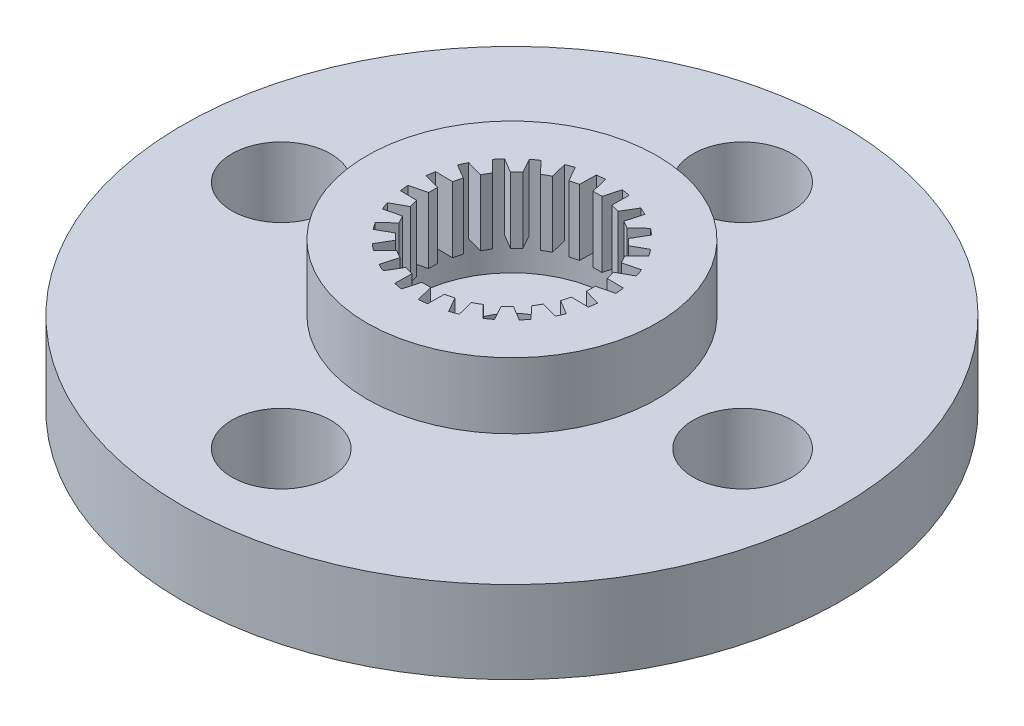
SolidWorks part; units mm, degrees
other "标注1"
sketch "草图15" plane through (-10, 4.5, 10) normal (-0.1683, 0.9847, 0.0463) x (-0.0875, -0.0617, 0.9943)
ref_plane "前视基准面" through (0, 0, 0) normal (0, 0, 1) x (1, 0, 0)
ref_plane "上视基准面" through (0, 0, 0) normal (0, 1, 0) x (1, 0, 0)
ref_plane "右视基准面" through (0, 0, 0) normal (1, 0, 0) x (0, 0, -1)
sketch "草图4" plane through (0, 0, 0) normal (0, 1, 0) x (1, 0, 0)
  circle A0 centre (0, 0) radius 10
  dimension "D1" = 20
extrude "凸台-拉伸2" add sketch "草图4" along normal blind 2.5
ref_plane "基准面7" through (0, 2.5, 0) normal (0, 1, 0) x (1, 0, 0)
sketch "草图6" plane through (0, 2.5, 0) normal (0, 1, 0) x (1, 0, 0)
  circle A0 centre (0, 0) radius 7 construction
  circle A1 centre (0, 7) radius 1.5
  circle A2 centre (0, 0) radius 1.5
  circle A3 centre (7, 0) radius 1.5
  circle A4 centre (-7, 0) radius 1.5
  circle A5 centre (0, -7) radius 1.5
  dimension "D1" = 3
  dimension "D2" = 3
  dimension "D3" = 3
  dimension "D4" = 3
  dimension "D5" = 3
  dimension "D6" = 14
extrude "切除-拉伸9" cut sketch "草图6" against normal blind 2.5
sketch "草图7" plane through (0, 2.5, 0) normal (0, 1, 0) x (1, 0, 0)
  circle A0 centre (0, 0) radius 4.4
  dimension "D1" = 8.8
extrude "凸台-拉伸3" add sketch "草图7" along normal blind 2
ref_plane "基准面8" through (0, 4.5, 0) normal (0, 1, 0) x (1, 0, 0)
sketch "草图8" plane through (0, 4.5, 0) normal (0, 1, 0) x (1, 0, 0)
  circle A0 centre (0, 0) radius 3
  dimension "D1" = 6
extrude "切除-拉伸10" cut sketch "草图8" against normal blind 3
ref_axis "基准轴1" through (0, 1.5, 0) along (0, 1, 0)
sketch "草图14" plane through (0, 4.5, 0) normal (0, 1, 0) x (1, 0, 0)
  line L0 (2.9769, -0.3715) -> (2.4958, -0.2354)
  line L1 (2.4958, -0.2354) -> (2.4958, 0.0323)
  line L2 (2.4958, 0.0323) -> (2.9958, 0.1588)
  arc A0 (2.9769, -0.3715) -> (2.9958, 0.1588) centre (0, 0) ccw
  dimension "D3" = 3
  dimension "D1" = 30
  dimension "D2" = 0.5
  dimension "0.5" = 0.5
extrude "凸台-拉伸5" add sketch "草图14" against normal blind 2
pattern_circular "阵列(圆周)1" count 24 over 360 about axis through (0, 4.5, 0) along (0, 1, 0) of "凸台-拉伸5"
